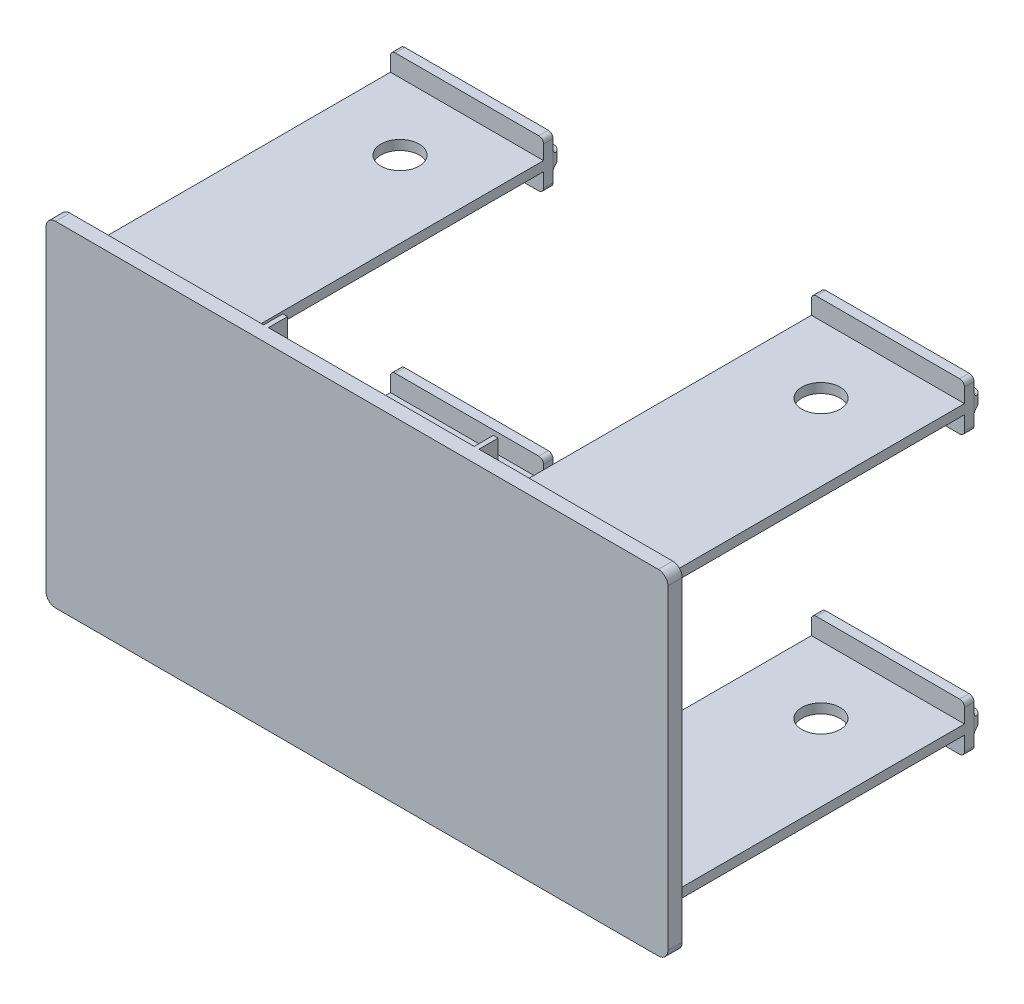
SolidWorks part; units mm, degrees
ref_plane "Front Plane" through (0, 0, 0) normal (0, 0, 1) x (1, 0, 0)
ref_plane "Top Plane" through (0, 0, 0) normal (0, 1, 0) x (1, 0, 0)
ref_plane "Right Plane" through (0, 0, 0) normal (1, 0, 0) x (0, 0, -1)
sketch "Sketch1" plane through (0, 0, 0) normal (0, 0, 1) x (1, 0, 0)
  line L1 (97, 49.75) -> (-97, 49.75)
  line L2 (97, 49.75) -> (97, -49.75)
  line L3 (97, -49.75) -> (-97, -49.75)
  line L4 (-97, 49.75) -> (-97, -49.75)
  line L5 (97, 49.75) -> (-97, -49.75) construction
  line L6 (97, -49.75) -> (-97, 49.75) construction
  point P0 (0, 0)
  dimension "D1" = 194
  dimension "D2" = 99.5
extrude "Boss-Extrude1" add sketch "Sketch1" against normal blind 3
sketch "Sketch3" plane through (0, 0, -3) normal (0, 0, -1) x (-1, 0, 0)
  line L6 (-60, 30) -> (-60, 28)
  line L7 (60, 30) -> (60, 28)
  line L8 (28, 30) -> (28, 28)
  line L9 (-28, 30) -> (-28, 28)
  line L10 (-60, 28) -> (-28, 28)
  line L11 (-60, -28) -> (-28, -28)
  line L12 (-60, -30) -> (-28, -30)
  line L13 (-60, 30) -> (-28, 30)
  line L14 (-60, -28) -> (-60, -30)
  line L15 (-60, 49.75) -> (-60, -49.75) construction
  line L18 (-28, -28) -> (-28, -30)
  line L19 (28, 28) -> (60, 28)
  line L20 (-28, 49.75) -> (-28, -49.75) construction
  line L21 (28, 30) -> (60, 30)
  line L22 (28, -28) -> (28, -30)
  line L23 (60, 49.75) -> (60, -49.75) construction
  line L24 (28, 49.75) -> (28, -49.75) construction
  line L25 (60, -28) -> (60, -30)
  line L26 (28, -28) -> (60, -28)
  line L29 (28, -30) -> (60, -30)
  point P20 (-97, 28)
  point P21 (97, 28)
  point P22 (-97, -28)
  point P23 (97, -28)
  point P24 (-97, -30)
  point P25 (97, -30)
  point P26 (-97, 30)
  point P27 (97, 30)
  dimension "D3" = 32
extrude "Boss-Extrude2" add sketch "Sketch3" along normal blind 68
sketch "Sketch4" plane through (0, 30, 0) normal (0, 1, 0) x (1, 0, 0)
  circle A0 centre (-44, 53) radius 4
  circle A1 centre (44, 53) radius 4
  dimension "D1" = 8
extrude "Cut-Extrude2" cut sketch "Sketch4" against normal blind 68
fillet "Fillet2" radius 2 24 edges at (-28, -29, -71) (-60, -29, -71) (28, -29, -71) (60, -29, -71) (-60, 29, -71) (-28, 29, -71) (28, 29, -71) (60, 29, -71) (44, 28, -3) (28, 29, -3) (60, 29, -3) (44, 30, -3) (-28, 29, -3) (-44, 28, -3) (-60, 29, -3) (-44, 30, -3) (44, -30, -3) (28, -29, -3) (44, -28, -3) (60, -29, -3) (-28, -29, -3) (-60, -29, -3) (-44, -30, -3) (-44, -28, -3)
sketch "Sketch6" plane through (0, 0, -3) normal (0, 0, -1) x (-1, 0, 0)
  line L0 (-22.5, 49.75) -> (-21.5, 49.75)
  line L3 (-22.5, 49.75) -> (-22.5, -49.75)
  line L4 (22.5, 49.75) -> (22.5, -49.75)
  line L5 (-21.5, 49.75) -> (-21.5, -49.75)
  line L6 (21.5, 49.75) -> (21.5, -49.75)
  line L7 (21.5, 49.75) -> (22.5, 49.75)
  line L8 (-22.5, -49.75) -> (-21.5, -49.75)
  line L9 (21.5, -49.75) -> (22.5, -49.75)
extrude "Boss-Extrude3" add sketch "Sketch6" along normal blind 4
fillet "Fillet3" radius 2 4 edges at (-22, -49.75, -7) (22, -49.75, -7) (22, 49.75, -7) (-22, 49.75, -7)
sketch "Sketch7" plane through (0, 30, 0) normal (0, 1, 0) x (1, 0, 0)
  line L2 (-44, 69) -> (-60, 69)
  line L3 (-60, 69) -> (-60, 5) construction
  line L4 (-44, 69) -> (-28, 69)
  line L5 (-28, 69) -> (-28, 5) construction
  line L6 (-60, 69) -> (-60, 67)
  line L7 (-60, 67) -> (-28, 67)
  line L8 (-28, 67) -> (-28, 69)
  line L10 (28, 67) -> (28, 69)
  line L11 (60, 67) -> (28, 67)
  line L12 (60, 69) -> (60, 67)
  line L13 (44, 69) -> (28, 69)
  line L14 (44, 69) -> (60, 69)
extrude "Boss-Extrude4" add sketch "Sketch7" along normal blind 4 and the other way blind 6
fillet "Fillet4" radius 1 12 edges at (60, 24, -68) (28, 24, -68) (-28, 24, -68) (-60, 24, -68) (-60, 34, -68) (-28, 34, -68) (60, 34, -68) (28, 34, -68) (44, 28, -69) (-44, 28, -69) (44, 30, -69) (-44, 30, -69)
sketch "Sketch8" plane through (0, -30, 0) normal (0, -1, 0) x (-1, 0, 0)
  line L2 (44, 69) -> (28, 69)
  line L3 (44, 69) -> (60, 69)
  line L4 (60, 69) -> (60, 67)
  line L5 (60, 67) -> (28, 67)
  line L6 (28, 67) -> (28, 69)
  line L8 (-28, 67) -> (-28, 69)
  line L9 (-60, 67) -> (-28, 67)
  line L10 (-60, 69) -> (-60, 67)
  line L11 (-44, 69) -> (-60, 69)
  line L12 (-44, 69) -> (-28, 69)
extrude "Boss-Extrude5" add sketch "Sketch8" along normal blind 4 and the other way blind 6
fillet "Fillet5" radius 1 12 edges at (28, -34, -68) (28, -24, -68) (-28, -34, -68) (-28, -24, -68) (60, -34, -68) (60, -24, -68) (-60, -34, -68) (-60, -24, -68) (44, -28, -69) (44, -30, -69) (-44, -30, -69) (-44, -28, -69)
fillet "Fillet6" radius 10 4 edges at (97, 49.75, -1.5) (97, -49.75, -1.5) (-97, -49.75, -1.5) (-97, 49.75, -1.5)
sketch "Sketch9" plane through (0, 0, 0) normal (0, 0, 1) x (1, 0, 0)
  line L6 (-65, 49.75) -> (-65, -49.75)
  line L7 (65, 49.75) -> (65, -49.75)
  line L14 (-65, 49.75) -> (-109.3579, 49.75)
  line L15 (-109.3579, 49.75) -> (-109.3579, -49.75)
  line L16 (-109.3579, -49.75) -> (-65, -49.75)
  line L17 (65, 49.75) -> (103.5707, 49.75)
  line L18 (103.5707, 49.75) -> (103.5707, -49.75)
  line L19 (103.5707, -49.75) -> (65, -49.75)
extrude "Cut-Extrude3" cut sketch "Sketch9" against normal blind 10
sketch "Sketch10" plane through (0, 0, 0) normal (0, 0, 1) x (1, 0, 0)
  line L3 (-65, -35) -> (65, -35)
  line L4 (-65, 35) -> (65, 35)
  line L5 (-65, 35) -> (-65, 49.75)
  line L6 (-65, 49.75) -> (65, 49.75)
  line L7 (65, 49.75) -> (65, 35)
  line L8 (-65, -35) -> (-65, -49.75)
  line L9 (-65, -49.75) -> (65, -49.75)
  line L10 (65, -49.75) -> (65, -35)
extrude "Cut-Extrude4" cut sketch "Sketch10" against normal blind 10
fillet "Fillet7" radius 2 4 edges at (65, 35, -1.5) (65, -35, -1.5) (-65, -35, -1.5) (-65, 35, -1.5)
